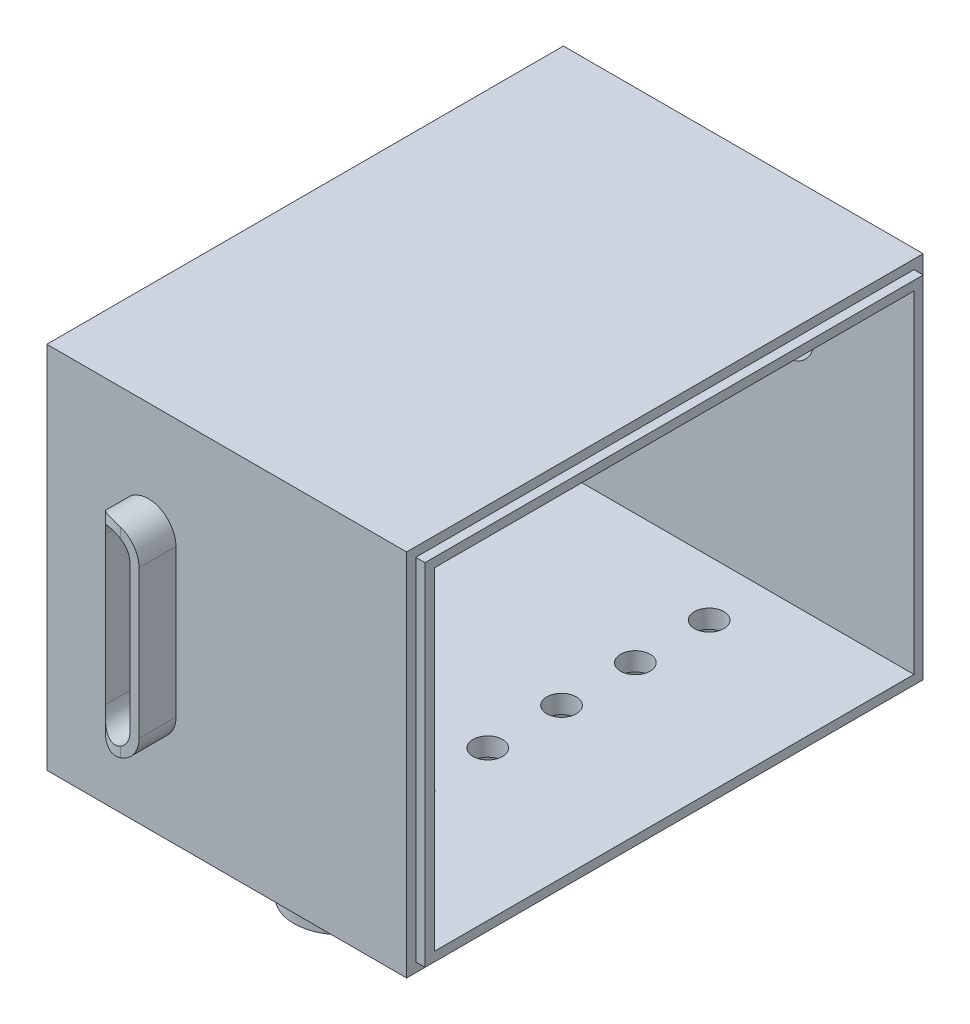
SolidWorks part; units mm, degrees
material "ABS"
ref_plane "Plan de face" through (0, 0, 0) normal (0, 0, 1) x (1, 0, 0)
ref_plane "Plan de dessus" through (0, 0, 0) normal (0, 1, 0) x (1, 0, 0)
ref_plane "Plan de droite" through (0, 0, 0) normal (1, 0, 0) x (0, 0, -1)
sketch "Esquisse2" plane through (0, 0, 0) normal (1, 0, 0) x (0, 0, -1)
  line L1 (0, 100) -> (140, 100)
  line L2 (0, 100) -> (0, 0)
  line L3 (0, 0) -> (140, 0)
  line L4 (140, 100) -> (140, 0)
  line L5 (5, 95) -> (135, 95)
  line L6 (5, 95) -> (5, 5)
  line L7 (5, 5) -> (135, 5)
  line L8 (135, 95) -> (135, 5)
  dimension "D1" = 140
  dimension "D2" = 100
  dimension "D3" = 0
  dimension "D4" = 5
  dimension "D5" = 5
  dimension "D6" = 5
  dimension "D7" = 5
extrude "Boss.-Extru.1" add sketch "Esquisse2" along normal blind 100
sketch "Esquisse3" plane through (0, 0, -140) normal (0, 0, -1) x (-1, 0, 0)
  line L0 (0, 95) -> (0, 5) construction
  line L2 (-100, 100) -> (0, 100) construction
  circle A0 centre (-65, 70) radius 8
  dimension "D1" = 16
  dimension "D2" = 65
  dimension "D3" = 30
extrude "Enlèv. mat.-Extru.1" cut sketch "Esquisse3" against normal blind 10
sketch "Esquisse5" plane through (0, 0, 0) normal (0, 0, 1) x (1, 0, 0)
  line L0 (100, 0) -> (0, 0) construction
  line L1 (0, 100) -> (5, 100)
  line L2 (0, 100) -> (0, 0)
  line L3 (0, 0) -> (5, 0)
  line L4 (5, 100) -> (5, 0)
  dimension "D1" = 5
extrude "Boss.-Extru.2" add sketch "Esquisse5" against normal blind 140
sketch "Esquisse6" plane through (100, 0, 0) normal (1, 0, 0) x (0, 0, -1)
  line L0 (140, 0) -> (140, 100) construction
  line L1 (0, 100) -> (140, 100)
  line L2 (0, 100) -> (0, 0)
  line L3 (0, 0) -> (140, 0)
  line L4 (140, 100) -> (140, 0)
  line L5 (140, 100) -> (0, 100) construction
  line L6 (0, 100) -> (0, 0) construction
  line L7 (0, 0) -> (140, 0) construction
  line L9 (2.5, 97.5) -> (137.5, 97.5)
  line L10 (2.5, 97.5) -> (2.5, 2.5)
  line L11 (2.5, 2.5) -> (137.5, 2.5)
  line L12 (137.5, 97.5) -> (137.5, 2.5)
  dimension "D1" = 0
  dimension "D2" = 0
  dimension "D3" = 0
  dimension "D4" = 0
  dimension "D5" = 2.5
  dimension "D6" = 2.5
  dimension "D7" = 2.5
  dimension "D8" = 2.5
extrude "Enlèv. mat.-Extru.2" cut sketch "Esquisse6" against normal blind 2.5
sketch "Esquisse9" plane through (0, 0, 0) normal (0, 0, 1) x (1, 0, 0)
  line L0 (27.5, 70) -> (27.5, 30) construction
  line L1 (35, 70) -> (35, 30)
  line L2 (20, 70) -> (20, 30)
  line L3 (0, 100) -> (0, 0) construction
  line L4 (97.5, 0) -> (0, 0) construction
  line L5 (27.5, 70) -> (27.5, 30) construction
  line L6 (32.5, 70) -> (32.5, 30)
  line L7 (22.5, 70) -> (22.5, 30)
  arc A0 (35, 70) -> (20, 70) centre (27.5, 70) ccw
  arc A1 (20, 30) -> (35, 30) centre (27.5, 30) ccw
  arc A2 (32.5, 70) -> (22.5, 70) centre (27.5, 70) ccw
  arc A3 (22.5, 30) -> (32.5, 30) centre (27.5, 30) ccw
  point P2 (27.5, 50)
  point P13 (27.5, 50)
  dimension "D3" = 40
  dimension "D4" = 50
  dimension "D1" = 20
  dimension "D2" = 15
  dimension "D5" = 2.5
extrude "Boss.-Extru.3" add sketch "Esquisse9" along normal blind 10
sketch "Esquisse11" plane through (0, 0, 0) normal (0, 0, 1) x (1, 0, 0)
  line L0 (27.5, 70) -> (27.5, 30) construction
  line L1 (32.5, 70) -> (32.5, 30)
  line L2 (22.5, 70) -> (22.5, 30)
  line L3 (32.5, 30) -> (32.5, 70) construction
  arc A0 (32.5, 70) -> (22.5, 70) centre (27.5, 70) ccw
  arc A1 (22.5, 30) -> (32.5, 30) centre (27.5, 30) ccw
  arc A2 (32.5, 70) -> (22.5, 70) centre (27.5, 70) ccw construction
  arc A4 (22.5, 30) -> (32.5, 30) centre (27.5, 30) ccw construction
  point P2 (27.5, 50)
  dimension "D1" = 0
  dimension "D2" = 0
  dimension "D3" = 0
extrude "Enlèv. mat.-Extru.3" cut sketch "Esquisse11" against normal blind 8
fillet "Congé1" radius 10 4 edges at (20, 50, 10) (20, 70, 5) (20, 30, 5) (22.5, 50, 10)
sketch "Esquisse12" plane through (0, 0, -140) normal (0, 0, -1) x (-1, 0, 0)
  line L0 (-27.5, 70) -> (-27.5, 30) construction
  line L1 (-20, 70) -> (-20, 30)
  line L2 (-35, 70) -> (-35, 30)
  line L3 (0, 0) -> (0, 100) construction
  line L4 (-97.5, 100) -> (0, 100) construction
  line L5 (-27.5, 70) -> (-27.5, 30) construction
  line L6 (-22.5, 70) -> (-22.5, 30)
  line L7 (-32.5, 70) -> (-32.5, 30)
  arc A0 (-20, 70) -> (-35, 70) centre (-27.5, 70) ccw
  arc A1 (-35, 30) -> (-20, 30) centre (-27.5, 30) ccw
  arc A2 (-22.5, 70) -> (-32.5, 70) centre (-27.5, 70) ccw
  arc A3 (-32.5, 30) -> (-22.5, 30) centre (-27.5, 30) ccw
  point P2 (-27.5, 50)
  point P13 (-27.5, 50)
  dimension "D1" = 40
  dimension "D2" = 20
  dimension "D3" = 15
  dimension "D4" = 50
  dimension "D5" = 2.5
extrude "Boss.-Extru.4" add sketch "Esquisse12" along normal blind 10
sketch "Esquisse13" plane through (0, 0, -140) normal (0, 0, -1) x (-1, 0, 0)
  line L0 (-27.5, 70) -> (-27.5, 30) construction
  line L1 (-22.5, 70) -> (-22.5, 30)
  line L2 (-32.5, 70) -> (-32.5, 30)
  line L3 (-22.5, 30) -> (-22.5, 70) construction
  line L4 (-32.5, 70) -> (-32.5, 30) construction
  arc A0 (-22.5, 70) -> (-32.5, 70) centre (-27.5, 70) ccw
  arc A1 (-32.5, 30) -> (-22.5, 30) centre (-27.5, 30) ccw
  arc A2 (-22.5, 70) -> (-32.5, 70) centre (-27.5, 70) ccw construction
  arc A3 (-32.5, 30) -> (-22.5, 30) centre (-27.5, 30) ccw construction
  point P2 (-27.5, 50)
  dimension "D3" = 0
  dimension "D4" = 0
  dimension "D1" = 0
  dimension "D2" = 0
extrude "Enlèv. mat.-Extru.4" cut sketch "Esquisse13" against normal blind 6
fillet "Congé2" radius 10 4 edges at (20, 50, -150) (20, 70, -145) (20, 30, -145) (22.5, 50, -150)
sketch "Esquisse15" plane through (0, 0, 0) normal (0, -1, 0) x (1, 0, 0)
  line L0 (97.5, -140) -> (0, -140) construction
  line L1 (97.5, -137.5) -> (97.5, -2.5) construction
  line L2 (97.5, -140) -> (97.5, 0) construction
  circle A0 centre (59.5, -120) radius 4
  circle A1 centre (59.5, -100) radius 4
  circle A2 centre (59.5, -80) radius 4
  circle A3 centre (59.5, -60) radius 4
  circle A4 centre (59.5, -40) radius 4
  circle A5 centre (59.5, -20) radius 4
  dimension "D8" = 8
  dimension "D9" = 8
  dimension "D10" = 8
  dimension "D11" = 8
  dimension "D12" = 8
  dimension "D13" = 8
  dimension "D1" = 20
  dimension "D2" = 20
  dimension "D3" = 20
  dimension "D4" = 20
  dimension "D5" = 20
  dimension "D6" = 20
  dimension "D7" = 38
  dimension "D14" = 38
  dimension "D15" = 38
  dimension "D16" = 38
  dimension "D17" = 38
  dimension "D18" = 38
extrude "Enlèv. mat.-Extru.5" cut sketch "Esquisse15" against normal blind 10
sketch "Esquisse16" plane through (0, 0, 0) normal (0, -1, 0) x (-1, 0, 0)
  line L0 (-59.5, 20) -> (-59.5, 120) construction
  line L1 (-69.5, 20) -> (-69.5, 120)
  line L2 (-49.5, 20) -> (-49.5, 120)
  line L3 (-59.5, 20) -> (-59.5, 120) construction
  line L4 (-72, 20) -> (-72, 120)
  line L5 (-47, 20) -> (-47, 120)
  arc A0 (-69.5, 20) -> (-49.5, 20) centre (-59.5, 20) ccw
  arc A1 (-49.5, 120) -> (-69.5, 120) centre (-59.5, 120) ccw
  arc A2 (-72, 20) -> (-47, 20) centre (-59.5, 20) ccw
  arc A3 (-47, 120) -> (-72, 120) centre (-59.5, 120) ccw
  point P4 (-59.5, 70)
  point P9 (-59.5, 70)
  dimension "D1" = 12.5
  dimension "D2" = 10
extrude "Boss.-Extru.5" add sketch "Esquisse16" along normal blind 10
